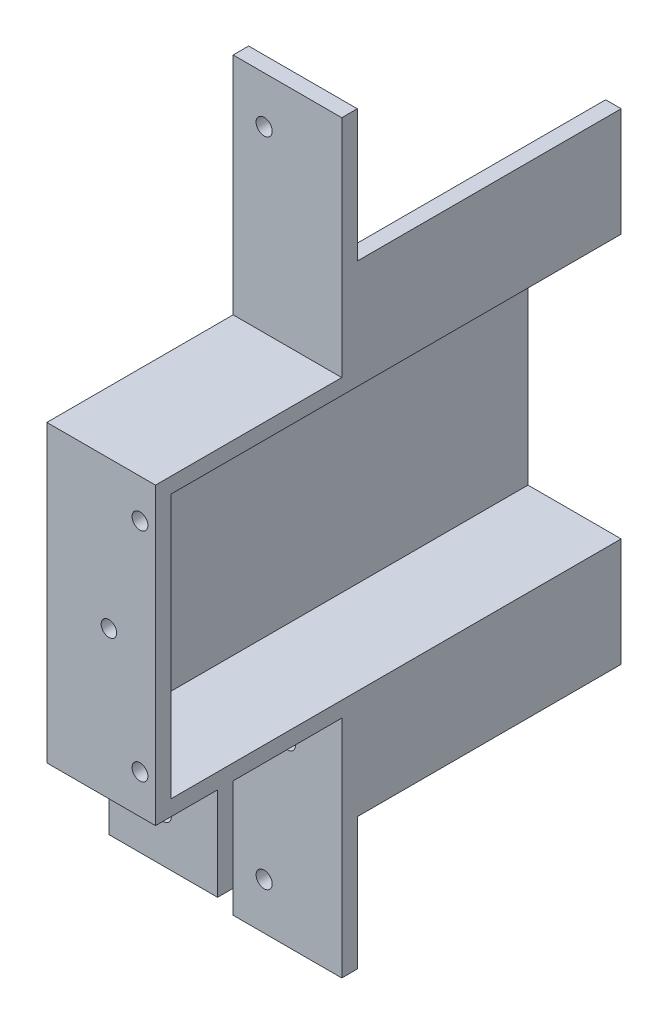
SolidWorks part; units mm, degrees
other "Markup2"
sketch "Sketch14" plane through (44.45, -152.4, 190.5) normal (0.8655, -0.4695, 0.1749) x (0.49, 0.866, -0.1002)
other "Markup3"
sketch "Sketch15" plane through (44.45, -152.4, 190.5) normal (0.8655, -0.4695, 0.1749) x (0.49, 0.866, -0.1002)
ref_plane "Front Plane" through (0, 0, 0) normal (0, 0, 1) x (1, 0, 0)
ref_plane "Top Plane" through (0, 0, 0) normal (0, 1, 0) x (1, 0, 0)
ref_plane "Right Plane" through (0, 0, 0) normal (1, 0, 0) x (0, 0, -1)
sketch "Sketch1" plane through (0, 0, 0) normal (0, 0, 1) x (1, 0, 0)
  line L0 (0, 0) -> (44.45, 0) construction
  line L5 (0, -60.325) -> (44.45, -60.325)
  line L6 (0, -60.325) -> (0, 60.325)
  line L7 (0, 60.325) -> (44.45, 60.325)
  line L8 (44.45, -60.325) -> (44.45, 60.325)
  dimension "D1" = 120.65
  dimension "D2" = 44.45
extrude "Boss-Extrude1" add sketch "Sketch1" along normal blind 190.5
sketch "Sketch2" plane through (0, 0, 0) normal (0, 0, -1) x (-1, 0, 0)
  line L0 (-44.45, -60.325) -> (-44.45, 60.325) construction
  line L1 (-6.35, -53.975) -> (-44.45, -53.975)
  line L2 (-6.35, -53.975) -> (-6.35, 53.975)
  line L3 (-6.35, 53.975) -> (-44.45, 53.975)
  line L4 (-44.45, -53.975) -> (-44.45, 53.975)
  line L5 (-6.35, -53.975) -> (-44.45, 53.975) construction
  line L6 (-6.35, 53.975) -> (-44.45, -53.975) construction
  line L7 (0, 60.325) -> (0, -60.325) construction
  line L8 (-44.45, 60.325) -> (0, 60.325) construction
  point P0 (-25.4, 0)
  dimension "D1" = 6.35
  dimension "D2" = 6.35
extrude "Cut-Extrude1" cut sketch "Sketch2" against normal offset from surface (184.15 mm away) 6.35 up to face at (22.225, 0, 190.5)
sketch "Sketch4" plane through (0, 0, 184.15) normal (0, 0, -1) x (-1, 0, 0)
  line L3 (-44.45, 0) -> (24.1169, 0) construction
  line L4 (-44.45, -53.975) -> (-44.45, 53.975) construction
  circle A0 centre (-38.1, 44.45) radius 3.2385
  circle A1 centre (-38.1, -44.45) radius 3.2385
  dimension "D3" = 6.477
  dimension "D1" = 6.35
  dimension "D2" = 88.9
sketch "Sketch5" plane through (0, 0, 184.15) normal (0, 0, -1) x (-1, 0, 0)
  line L0 (-6.35, -53.975) -> (-6.35, 53.975) construction
  circle A0 centre (-25.4, 0) radius 3.175
  dimension "D2" = 6.35
  dimension "D1" = 19.05
extrude "Cut-Extrude2" cut sketch "Sketch5" against normal through all
sketch "Sketch8" plane through (0, 0, 0) normal (0, 0, 1) x (1, 0, 0)
  line L1 (0, -60.325) -> (44.45, -60.325)
  line L2 (0, -60.325) -> (0, -98.425)
  line L3 (0, -98.425) -> (44.45, -98.425)
  line L4 (44.45, -60.325) -> (44.45, -98.425)
  circle A0 centre (22.225, -79.375) radius 3.302
  dimension "D1" = 6.604
  dimension "D2" = 19.05
  dimension "D3" = 22.225
  dimension "D4" = 38.1
extrude "Boss-Extrude6" add sketch "Sketch8" along normal blind 6.35 from offset 158.75
extrude "Boss-Extrude7" add sketch "Sketch8<2>" along normal blind 6.35 from offset 107.95
sketch "Sketch8<2>" plane through (0, 0, 0) normal (0, 0, 1) x (1, 0, 0) same geometry as "Sketch8"
sketch "Sketch10" plane through (0, -60.325, 0) normal (0, -1, 0) x (1, 0, 0)
  line L0 (0, 107.95) -> (44.45, 107.95) construction
  line L1 (44.45, 0) -> (38.1, 0)
  line L2 (44.45, 0) -> (44.45, 107.95)
  line L3 (44.45, 107.95) -> (38.1, 107.95)
  line L4 (38.1, 0) -> (38.1, 107.95)
  dimension "D1" = 6.35
extrude "Boss-Extrude9" add sketch "Sketch10" along normal blind 38.1
extrude "Boss-Extrude10" add sketch "Sketch10<2>" against normal blind 38.1 from surface starting at face at (22.225, 60.325, 95.25)
sketch "Sketch10<2>" plane through (0, -60.325, 0) normal (0, -1, 0) x (1, 0, 0) same geometry as "Sketch10"
sketch "Sketch11" plane through (0, -98.425, 0) normal (0, -1, 0) x (1, 0, 0)
  line L1 (44.45, 114.3) -> (0, 114.3)
  line L2 (44.45, 114.3) -> (44.45, 107.95)
  line L3 (44.45, 107.95) -> (0, 107.95)
  line L4 (0, 114.3) -> (0, 107.95)
extrude "Boss-Extrude11" add sketch "Sketch11" along normal blind 53.975
extrude "Boss-Extrude12" add sketch "Sketch11<4>" against normal blind 92.075 from surface starting at face at (27.5167, 60.325, 99.4833)
sketch "Sketch11<4>" plane through (0, -98.425, 0) normal (0, -1, 0) x (1, 0, 0) same geometry as "Sketch11"
sketch "Sketch12" plane through (0, 0, 114.3) normal (0, 0, 1) x (1, 0, 0)
  line L0 (0, 152.4) -> (0, 60.325) construction
  line L2 (-49.5294, 0) -> (176.7217, 0) construction
  circle A0 centre (12.7, 133.35) radius 3.302
  circle A1 centre (12.7, -133.35) radius 3.302
  dimension "D1" = 6.604
  dimension "D2" = 12.7
  dimension "D3" = 133.35
extrude "Cut-Extrude3" cut sketch "Sketch12" against normal through all
extrude "Cut-Extrude4" cut sketch "Sketch4" against normal through all both
equation "\"tightTol\" = 0.005in"
equation "\"normTol\"= 0.01in"
equation "\"looseTol\"= 0.02in"
equation "\"D3@Sketch4\"=\"tightTol\"+0.250000in"
equation "\"D1@Sketch8\"=\"normTol\"+0.250000in"
equation "\"D1@Sketch12\"=\"normTol\"+0.250000in"
